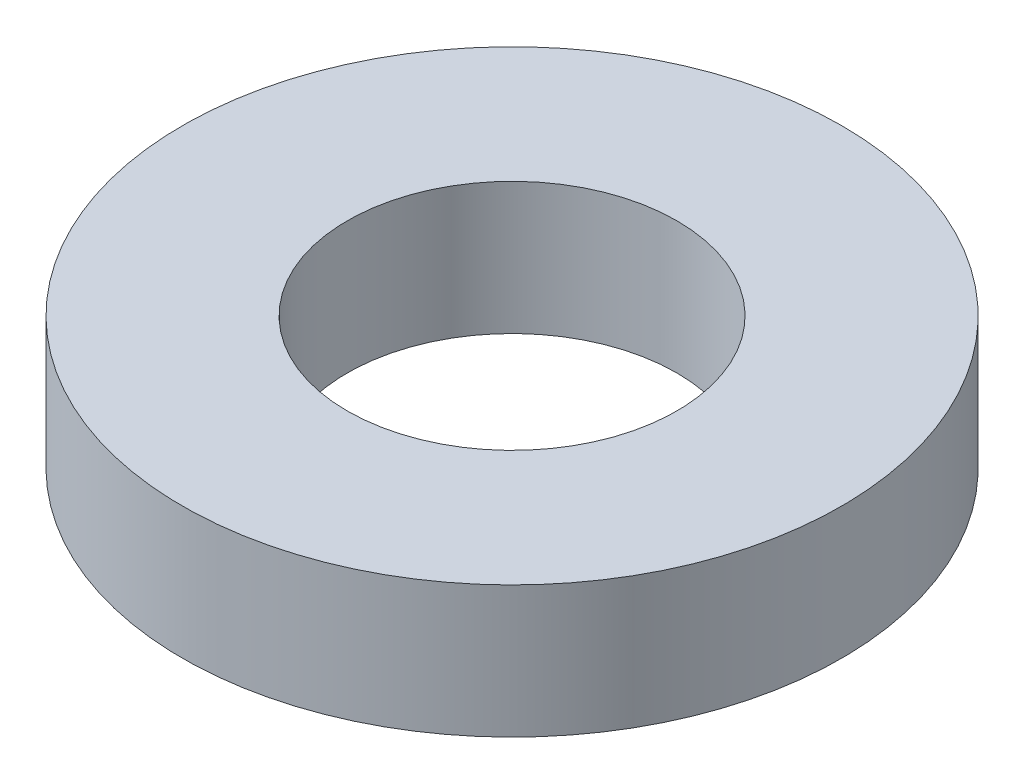
SolidWorks part; units mm, degrees
material "VITON"
ref_plane "Front Plane" through (0, 0, 0) normal (0, 0, 1) x (1, 0, 0)
ref_plane "Top Plane" through (0, 0, 0) normal (0, 1, 0) x (1, 0, 0)
ref_plane "Right Plane" through (0, 0, 0) normal (1, 0, 0) x (0, 0, -1)
ref_axis "Axis1" through (0, 1.43, 0) along (0, -1, 0)
sketch "Sketch1" plane through (0, 0, 0) normal (0, 0, 1) x (1, 0, 0)
  line L0 (0, 0) -> (3.75, 0) construction
  line L1 (3.75, 0) -> (5.25, 0) construction
  line L2 (0, 0) -> (0, 1) construction
  line L4 (2.5, 1) -> (5, 1)
  line L5 (2.5, 1) -> (2.5, -1)
  line L6 (2.5, -1) -> (5, -1)
  line L7 (5, 1) -> (5, -1)
  line L8 (2.5, 1) -> (5, -1) construction
  line L9 (2.5, -1) -> (5, 1) construction
  dimension "D1" = 10
  dimension "D2" = 2.5
  dimension "D3" = 1
  dimension "D4" = 2
revolve "Revolve1" add sketch "Sketch1" angle 360 about L2
